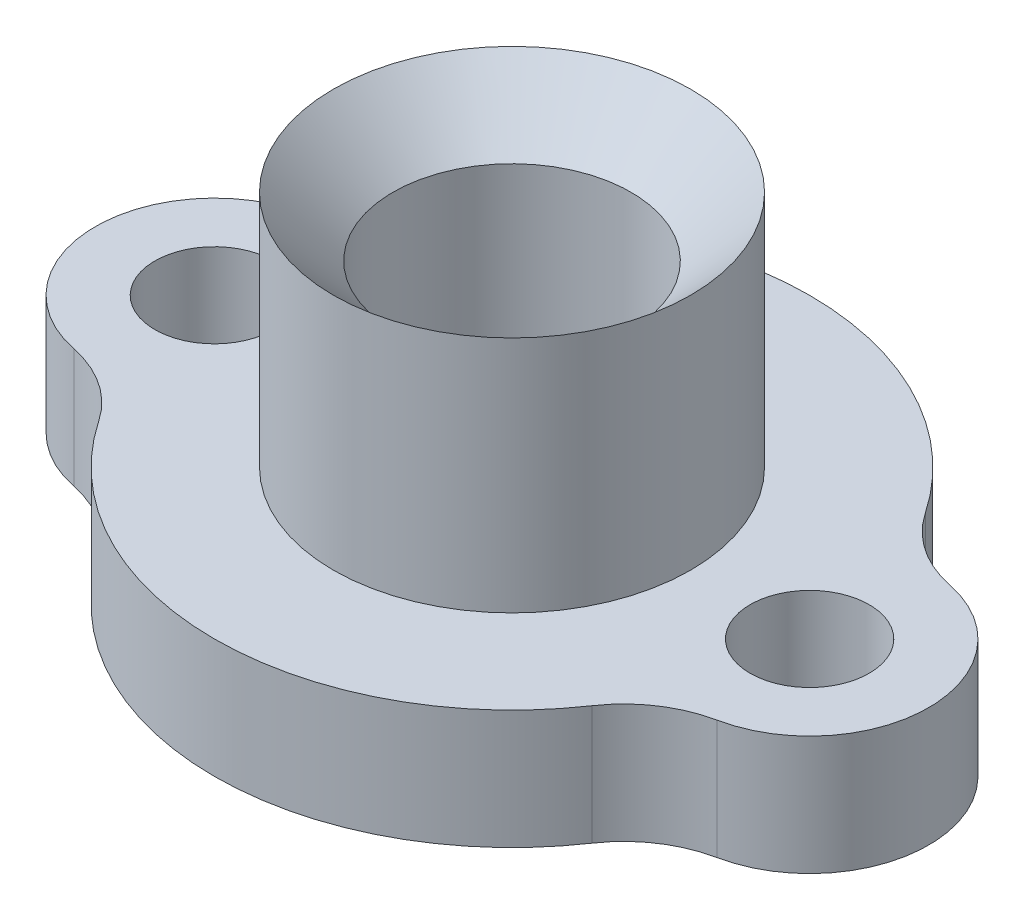
SolidWorks part; units mm, degrees
ref_plane "Front Plane" through (0, 0, 0) normal (0, 0, 1) x (1, 0, 0)
ref_plane "Top Plane" through (0, 0, 0) normal (0, 1, 0) x (1, 0, 0)
ref_plane "Right Plane" through (0, 0, 0) normal (1, 0, 0) x (0, 0, -1)
sketch "Sketch1" plane through (0, 0, 0) normal (0, 1, 0) x (1, 0, 0)
  line L0 (0, -34.191) -> (0, 37.2451) construction
  line L1 (-44.1648, 0) -> (70.8167, 0) construction
  arc A15 (-20.7143, -13.9971) -> (20.7143, -13.9971) centre (0, 0) ccw
  arc A16 (-27, 9.798) -> (-27, -9.798) centre (-25, 0) ccw
  arc A17 (-20.7143, -13.9971) -> (-27, -9.798) centre (-29, -19.5959) ccw
  arc A18 (-20.7143, 13.9971) -> (-27, 9.798) centre (-29, 19.5959) cw
  arc A19 (20.7143, -13.9971) -> (27, -9.798) centre (29, -19.5959) cw
  arc A20 (27, 9.798) -> (27, -9.798) centre (25, 0) cw
  arc A21 (20.7143, 13.9971) -> (27, 9.798) centre (29, 19.5959) ccw
  arc A22 (20.7143, 13.9971) -> (-20.7143, 13.9971) centre (0, 0) ccw
  circle A23 centre (25, 0) radius 5
  circle A24 centre (-25, 0) radius 5
  dimension "D1" = 20
  dimension "D2" = 50
  dimension "D3" = 20
extrude "Boss-Extrude1" add sketch "Sketch1" along normal blind 10
sketch "Sketch2" plane through (0, 10, 0) normal (0, 1, 0) x (1, 0, 0)
  circle A0 centre (0, 0) radius 15
  circle A1 centre (0, 0) radius 10
extrude "Boss-Extrude2" add sketch "Sketch2" along normal blind 25
chamfer "Chamfer2" distance 10 angle 45 1 edges at (0, 35, 10) tangent propagation no
